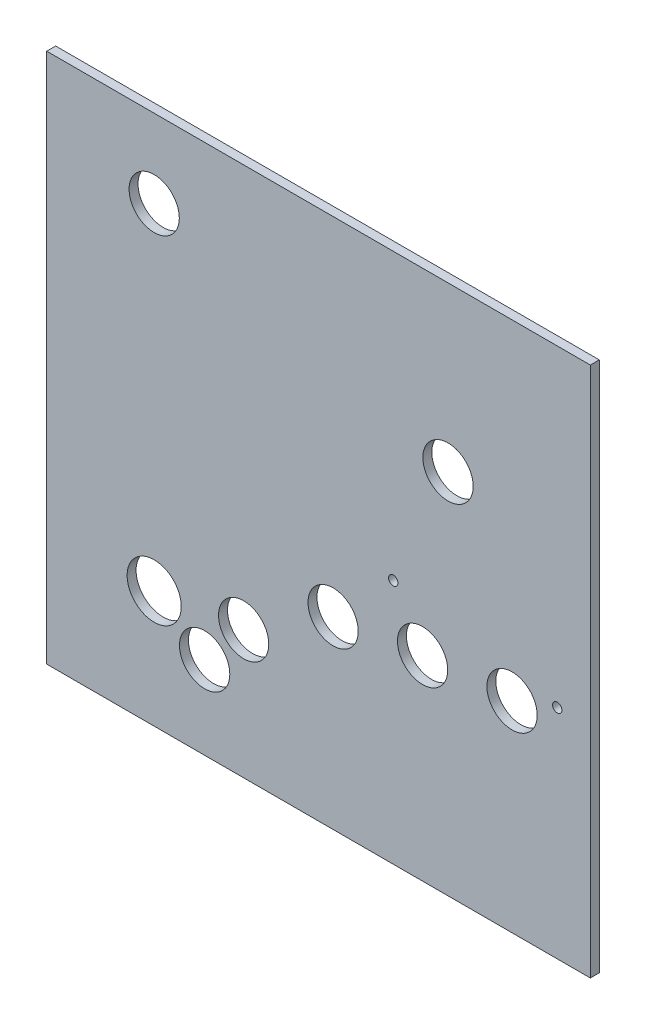
SolidWorks part; units mm, degrees
ref_plane "Front Plane" through (0, 0, 0) normal (0, 0, 1) x (1, 0, 0)
ref_plane "Top Plane" through (0, 0, 0) normal (0, 1, 0) x (1, 0, 0)
ref_plane "Right Plane" through (0, 0, 0) normal (1, 0, 0) x (0, 0, -1)
sketch "Sketch1" plane through (0, 0, 0) normal (0, 0, 1) x (1, 0, 0)
  line L8 (80.8024, 92.9856) -> (-227.8685, 92.9856)
  line L9 (-227.8685, 92.9856) -> (-227.8685, -208.4458)
  line L14 (-227.8685, -208.4458) -> (80.8024, -208.4458)
  line L15 (80.8024, -208.4458) -> (80.8024, 92.9856)
  circle A0 centre (0, 0) radius 14.2875
  circle A1 centre (-138.2019, -161.439) radius 14.2875
  circle A13 centre (-166.8476, 48.5356) radius 14.2621
  circle A14 centre (-166.8476, -141.9644) radius 15.3659
  circle A15 centre (-116.0476, -135.6144) radius 14.2621
  circle A16 centre (-65.2476, -103.8644) radius 14.2621
  circle A17 centre (-14.4476, -97.5144) radius 14.2621
  circle A19 centre (36.3524, -94.3893) radius 14.2875
  circle A20 centre (-31.0974, -68.8855) radius 3.1379 construction
  circle A21 centre (61.9974, -84.8561) radius 3.1355 construction
  circle A22 centre (-31.0974, -68.8855) radius 2.667
  circle A23 centre (61.9974, -84.8561) radius 2.667
  point P25 (-138.2019, -161.439)
  dimension "D1" = 6.2758
  dimension "D2" = 6.271
extrude "Boss-Extrude1" add sketch "Sketch1" along normal blind 5.08 contours L8 L15 A17 A16 A15 A14 A13 A1 A0 region at (-73.159, -55.9859, 0)
